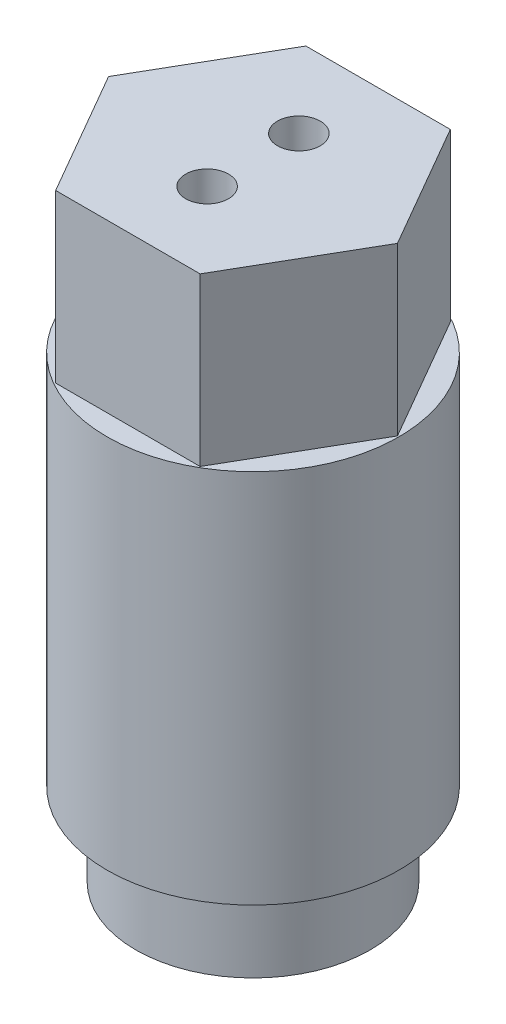
SolidWorks part; units mm, degrees
material "6061 Alloy"
ref_plane "Front Plane" through (0, 0, 0) normal (0, 0, 1) x (1, 0, 0)
ref_plane "Top Plane" through (0, 0, 0) normal (0, 1, 0) x (1, 0, 0)
ref_plane "Right Plane" through (0, 0, 0) normal (1, 0, 0) x (0, 0, -1)
sketch "Main Body Profile" plane through (0, 0, 0) normal (0, 1, 0) x (1, 0, 0)
  circle A0 centre (0, 0) radius 11.1125
  dimension "D1" = 22.225
extrude "Main Body Extrude" add sketch "Main Body Profile" along normal blind 28.575 contours A0
sketch "Hexagon Profile" plane through (0, 28.575, 0) normal (0, 1, 0) x (1, 0, 0)
  line L1 (5.4993, 9.525) -> (-5.4993, 9.525)
  line L2 (-5.4993, 9.525) -> (-10.9985, 0)
  line L3 (-10.9985, 0) -> (-5.4993, -9.525)
  line L4 (-5.4993, -9.525) -> (5.4993, -9.525)
  line L5 (5.4993, -9.525) -> (10.9985, 0)
  line L6 (10.9985, 0) -> (5.4993, 9.525)
  circle A0 centre (0, 0) radius 9.525 construction
  dimension "D1" = 19.05
extrude "Hexagon Body" add sketch "Hexagon Profile" along normal blind 12.7
sketch "Tip Profile" plane through (0, 0, 0) normal (0, -1, 0) x (1, 0, 0)
  circle A0 centre (0, 0) radius 8.9281
  dimension "D1" = 17.8562
extrude "Tip Body" add sketch "Tip Profile" along normal blind 6.35
sketch "Reference Sketch" plane through (0, -6.35, 0) normal (0, -1, 0) x (1, 0, 0)
  circle A0 centre (0, 0) radius 6.35
  dimension "D1" = 12.7
hole_wizard "Back Powder Hole" positions "Sketch9" profile "Sketch8" hole size "1/2" standard "ANSI Inch"
sketch "Sketch9" plane through (0, -6.35, 0) normal (0, -1, 0) x (-1, 0, 0)
  point P0 (0, 0)
sketch "Sketch8" plane through (0, -6.35, 0) normal (1, 0, 0) x (0, 0, -1)
  line L0 (0, 0) -> (0, 34.925)
  line L1 (0, 34.925) -> (6.35, 31.1095)
  line L2 (6.35, 31.1095) -> (6.35, 0)
  line L5 (6.35, 0) -> (0, 0)
  line L10 (0, 34.925) -> (-6.35, 31.1095) construction
  line L11 (0, -6.35) -> (0, 107.95) construction
  dimension "Hole Dia." = 12.7
  dimension "Hole Depth" = 34.925
  dimension "Drill Angle" = 118
ref_plane "Countersink Plane" through (0, 33.8966, 0) normal (0, 1, 0) x (1, 0, 0)
sketch "Sketch5" plane through (0, 33.8966, 0) normal (0, 1, 0) x (1, 0, 0)
  line L0 (0, 9.525) -> (0, -9.525) construction
  line L2 (5.4993, 9.525) -> (-5.4993, 9.525) construction
  line L3 (-5.4993, -9.525) -> (5.4993, -9.525) construction
  circle A1 centre (0, 3.4925) radius 1.7463
  circle A2 centre (0, -3.4925) radius 1.7462
  point P8 (0, 3.4925)
  point P10 (0, -3.4925)
  dimension "D1" = 3.4925
  dimension "D3" = 3.4925
  dimension "D2" = 3.4925
hole_wizard "Screw Holes" positions "Sketch5" profile "Sketch11" countersink size "#4" standard "ANSI Inch" end condition through all
sketch "Sketch11" plane through (0, 33.8966, 3.4925) normal (1, 0, 0) x (0, 0, -1)
  line L0 (0, 0) -> (0, 7.3784)
  line L1 (0, 7.3784) -> (1.6319, 7.3784)
  line L2 (1.6319, 7.3784) -> (1.6319, 1.0284)
  line L3 (1.6319, 1.0284) -> (2.8575, 0)
  line L5 (2.8575, 0) -> (0, 0)
  line L6 (-1.6319, 1.0284) -> (-2.8575, 0) construction
  line L11 (0, -6.35) -> (0, 107.95) construction
  dimension "Thru Hole Dia." = 3.2639
  dimension "Thru Hole Depth" = 7.3784
  dimension "Near C'Sink Dia." = 5.715
  dimension "Near C'Sink Angle" = 100
sketch "Sketch12" plane through (0, 33.8966, 0) normal (0, 1, 0) x (1, 0, 0)
  circle A0 centre (0, 3.4925) radius 2.8575
  circle A1 centre (0, -3.4925) radius 2.8575
  circle A2 centre (0, 0) radius 6.35 construction
extrude "Through Holes" cut sketch "Sketch12" against normal through all
sketch "Sketch13" plane through (0, 0, 0) normal (0, 0, 1) x (1, 0, 0)
  line L0 (0, 0) -> (0, -6.35) construction
  line L1 (-6.35, -6.35) -> (6.35, -6.35) construction
  line L2 (-8.9281, 0) -> (-7.6962, 0)
  line L3 (-8.9281, 0) -> (8.9281, 0) construction
  line L4 (-7.6962, 0) -> (-8.9281, -0.7112)
  line L5 (-8.9281, 0) -> (-8.9281, -6.35) construction
  line L6 (-8.9281, -0.7112) -> (-8.9281, 0)
  dimension "D1" = 0.7112
  dimension "D2" = 1.4225
revolve "Revolved Cut" cut sketch "Sketch13" angle 360 about L0
